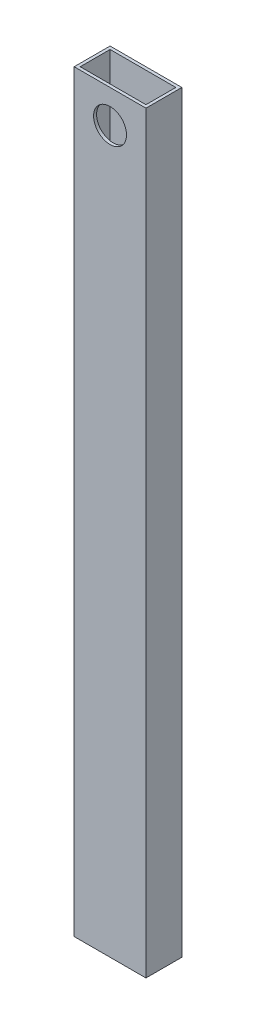
SolidWorks part; units mm, degrees
material "6061-T6 (SS)"
ref_plane "Front Plane" through (0, 0, 0) normal (0, 0, 1) x (1, 0, 0)
ref_plane "Top Plane" through (0, 0, 0) normal (0, 1, 0) x (1, 0, 0)
ref_plane "Right Plane" through (0, 0, 0) normal (1, 0, 0) x (0, 0, -1)
sketch "Sketch1" plane through (0, 0, 0) normal (0, 1, 0) x (1, 0, 0)
  line L1 (-38.1, 19.05) -> (38.1, 19.05)
  line L2 (-38.1, 19.05) -> (-38.1, -19.05)
  line L3 (-38.1, -19.05) -> (38.1, -19.05)
  line L4 (38.1, 19.05) -> (38.1, -19.05)
  line L5 (-38.1, 19.05) -> (38.1, -19.05) construction
  line L6 (-38.1, -19.05) -> (38.1, 19.05) construction
  point P0 (0, 0)
  dimension "D1" = 76.2
  dimension "D2" = 38.1
extrude "Extrude-Thin1" add sketch "Sketch1" along normal blind 510 and the other way blind 290 thin thin type one direction reverse wall 3.175
hole_wizard "Ø12.0 (12) Diameter Hole1" positions "Sketch2" profile "Sketch3" hole size "Ø12.0" standard "ANSI Metric" end condition up to next
sketch "Sketch2" plane through (0, 0, -19.05) normal (0, 0, -1) x (-1, 0, 0)
  line L1 (-20, -25) -> (20, -25)
  line L2 (-20, -25) -> (-20, -275)
  line L3 (-20, -275) -> (20, -275)
  line L4 (20, -25) -> (20, -275)
  line L5 (0, 55) -> (0, -55) construction
  line L6 (-38.1, -290) -> (38.1, -290) construction
  point P1 (-20, -25)
  point P2 (20, -275)
  point P69 (-20, -275)
  point P70 (20, -25)
  point P71 (0, -275)
  dimension "D1" = 40
  dimension "D2" = 25
  dimension "D3" = 15
sketch "Sketch3" plane through (20, -25, -19.05) normal (1, 0, 0) x (0, 1, 0)
  line L0 (0, 0) -> (0, 3.175)
  line L1 (0, 3.175) -> (6, 3.175)
  line L2 (6, 3.175) -> (6, 0)
  line L5 (6, 0) -> (0, 0)
  line L11 (0, -6.35) -> (0, 107.95) construction
  dimension "Thru Hole Dia." = 12
  dimension "Thru Hole Depth" = 3.175
sketch "Sketch6" plane through (0, 0, 19.05) normal (0, 0, 1) x (1, 0, 0)
  line L0 (0, -55) -> (0, 55) construction
  line L1 (-38.1, 510) -> (38.1, 510) construction
  circle A0 centre (0, 475) radius 17.5
  dimension "D1" = 35
  dimension "D2" = 35
extrude "Cut-Extrude1" cut sketch "Sketch6" against normal up to next
sketch "Sketch7" plane through (0, 0, -19.05) normal (0, 0, -1) x (-1, 0, 0)
  line L0 (0, 55) -> (0, -55) construction
  circle A0 centre (0, -75) radius 17.5
  dimension "D1" = 35
  dimension "D2" = 75
extrude "Cut-Extrude2" cut sketch "Sketch7" against normal up to next
